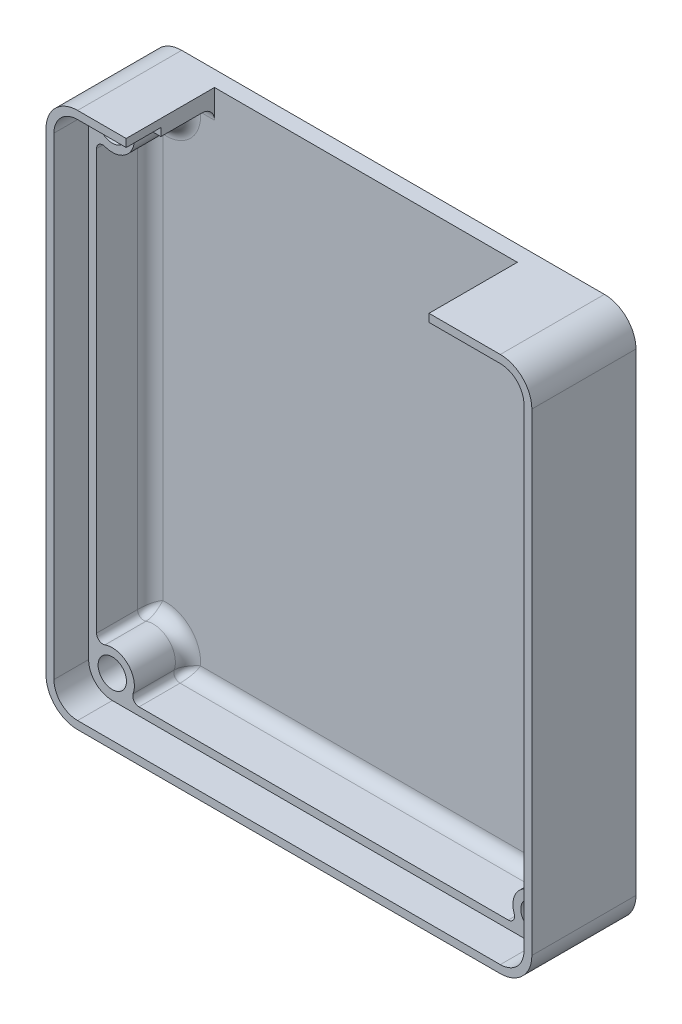
SolidWorks part; units mm, degrees
ref_plane "Plan de face" through (0, 0, 0) normal (0, 0, 1) x (1, 0, 0)
ref_plane "Plan de dessus" through (0, 0, 0) normal (0, 1, 0) x (1, 0, 0)
ref_plane "Plan de droite" through (0, 0, 0) normal (1, 0, 0) x (0, 0, -1)
sketch "Esquisse1" plane through (0, 0, 0) normal (0, 0, 1) x (1, 0, 0)
  line L1 (-38.5, -42.5) -> (38.5, -42.5)
  line L2 (-38.5, -42.5) -> (-38.5, 42.5)
  line L3 (-38.5, 42.5) -> (38.5, 42.5)
  line L4 (38.5, -42.5) -> (38.5, 42.5)
  line L5 (-38.5, -42.5) -> (38.5, 42.5) construction
  line L6 (-38.5, 42.5) -> (38.5, -42.5) construction
  point P0 (0, 0)
  dimension "D1" = 77
  dimension "D2" = 85
extrude "Boss.-Extru.1" add sketch "Esquisse1" along normal blind 16.5
fillet "Congé1" radius 5 4 edges at (-38.5, -42.5, 8.25) (38.5, -42.5, 8.25) (-38.5, 42.5, 8.25) (38.5, 42.5, 8.25)
shell "Coque1" thickness 2.5 removed face at (0, 0, 16.5)
sketch "Esquisse6" plane through (0, 0, 2.5) normal (0, 0, 1) x (1, 0, 0)
  circle A0 centre (-33.5, 37.5) radius 3.5
  circle A1 centre (33.5, 37.5) radius 3.5
  circle A2 centre (-33.5, -37.5) radius 3.5
  circle A3 centre (33.5, -37.5) radius 3.5
  dimension "D1" = 7
  dimension "D2" = 67
  dimension "D3" = 75
  dimension "D4" = 37.5
  dimension "D5" = 33.5
extrude "Boss.-Extru.2" add sketch "Esquisse6" along normal up to surface (14 mm away) up to face at (0, 0, 16.5)
fillet "Congé2" radius 1 8 edges at (-31.0505, -40, 9.5) (-36, -35.0505, 9.5) (36, -35.0505, 9.5) (31.0505, -40, 9.5) (36, 35.0505, 9.5) (31.0505, 40, 9.5) (-31.0505, 40, 9.5) (-36, 35.0505, 9.5)
sketch "Esquisse2" plane through (0, 0, 16.5) normal (0, 0, 1) x (1, 0, 0)
  line L16 (-37.25, 37.5) -> (-37.25, -37.5)
  line L17 (-33.5, -41.25) -> (33.5, -41.25)
  line L18 (37.25, -37.5) -> (37.25, 37.5)
  line L19 (33.5, 41.25) -> (-33.5, 41.25)
  line L20 (-37.25, 37.5) -> (-37.25, -37.5)
  line L21 (-33.5, -41.25) -> (33.5, -41.25)
  line L22 (37.25, -37.5) -> (37.25, 37.5)
  line L23 (33.5, 41.25) -> (-33.5, 41.25)
  arc A8 (-33.5, 41.25) -> (-37.25, 37.5) centre (-33.5, 37.5) ccw
  arc A9 (-37.25, -37.5) -> (-33.5, -41.25) centre (-33.5, -37.5) ccw
  arc A10 (33.5, -41.25) -> (37.25, -37.5) centre (33.5, -37.5) ccw
  arc A11 (37.25, 37.5) -> (33.5, 41.25) centre (33.5, 37.5) ccw
  arc A16 (-33.5, 41.25) -> (-37.25, 37.5) centre (-33.5, 37.5) ccw
  arc A17 (-37.25, -37.5) -> (-33.5, -41.25) centre (-33.5, -37.5) ccw
  arc A18 (33.5, -41.25) -> (37.25, -37.5) centre (33.5, -37.5) ccw
  arc A19 (37.25, 37.5) -> (33.5, 41.25) centre (33.5, 37.5) ccw
  dimension "D1" = 1.25
extrude "Enlèv. mat.-Extru.1" cut sketch "Esquisse2" against normal blind 5.5
sketch "Esquisse3" plane through (0, 0, 16.5) normal (0, 0, 1) x (1, 0, 0)
  line L0 (38.5, -37.5) -> (38.5, 37.5) construction
  line L1 (-25.8, 30) -> (22.2, 30)
  line L2 (-25.8, 30) -> (-25.8, 50)
  line L3 (-25.8, 50) -> (22.2, 50)
  line L4 (22.2, 30) -> (22.2, 50)
  line L5 (-25.8, 30) -> (22.2, 50) construction
  line L6 (-25.8, 50) -> (22.2, 30) construction
  point P0 (-1.8, 40)
  dimension "D1" = 16.3
  dimension "D2" = 48
  dimension "D3" = 20
  dimension "D4" = 30
extrude "Enlèv. mat.-Extru.2" cut sketch "Esquisse3" against normal blind 14
hole_wizard "Fraisage pour vis à tête fraisée M41" positions "Esquisse4" profile "Esquisse5" countersink size "M4" standard "ISO" end condition through all
sketch "Esquisse4" plane through (0, 0, 0) normal (0, 0, -1) x (-1, 0, 0)
  point P0 (-33.5, 37.5)
  point P2 (33.5, 37.5)
  point P4 (33.5, -37.5)
  point P6 (-33.5, -37.5)
  dimension "D1" = 67
  dimension "D2" = 75
  dimension "D3" = 37.5
  dimension "D4" = 33.5
sketch "Esquisse5" plane through (33.5, 37.5, 0) normal (1, 0, 0) x (0, 1, 0)
  line L0 (0, 0) -> (0, 16.5)
  line L1 (0, 16.5) -> (2.25, 16.5)
  line L2 (2.25, 16.5) -> (2.25, 2.45)
  line L3 (2.25, 2.45) -> (4.7, 0)
  line L5 (4.7, 0) -> (0, 0)
  line L6 (-2.25, 2.45) -> (-4.7, 0) construction
  line L11 (0, -6.35) -> (0, 107.95) construction
  dimension "Diamètre du perçage jusqu'au prochain" = 4.5
  dimension "Profondeur du perçage jusqu'au prochain" = 16.5
  dimension "Diamètre du fraisage entrant" = 9.4
  dimension "Angle du fraisage entrant" = 90
fillet "Congé3" radius 2 17 edges at (25.7287, 40, 2.5) (30.0739, 39.5774, 2.5) (31.0251, 35.0251, 2.5) (35.5774, 34.0739, 2.5) (36, 0, 2.5) (35.5774, -34.0739, 2.5) (31.0251, -35.0251, 2.5) (30.0739, -39.5774, 2.5) (0, -40, 2.5) (-30.0739, -39.5774, 2.5) (-31.0251, -35.0251, 2.5) (-35.5774, -34.0739, 2.5) (-36, 0, 2.5) (-35.5774, 34.0739, 2.5) (-31.0251, 35.0251, 2.5) (-30.0739, 39.5774, 2.5) (-27.5287, 40, 2.5)
equation "\"D3@Esquisse4\"=\"D2@Esquisse4\"/2"
equation "\"D4@Esquisse4\"=\"D1@Esquisse4\"/2"
equation "\"D4@Esquisse6\"=\"D3@Esquisse6\"/2"
equation "\"D5@Esquisse6\"=\"D2@Esquisse6\"/2"
